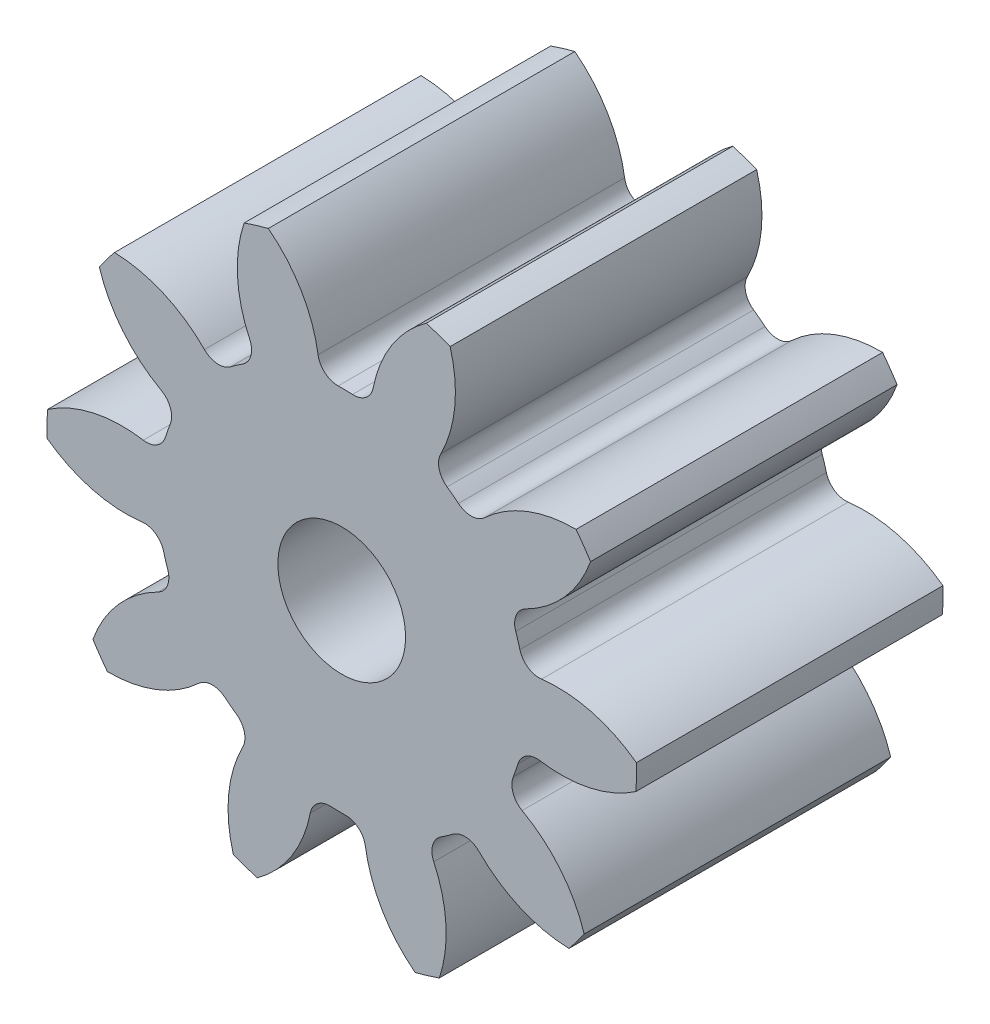
SolidWorks part; units mm, degrees
ref_plane "Front" through (0, 0, 0) normal (0, 0, 1) x (1, 0, 0)
ref_plane "Top" through (0, 0, 0) normal (0, 1, 0) x (1, 0, 0)
ref_plane "Right" through (0, 0, 0) normal (1, 0, 0) x (0, 0, -1)
sketch "Sketch3" plane through (0, 0, 0) normal (0, 0, 1) x (1, 0, 0)
  circle A0 centre (0, 0) radius 5.8615
  dimension "od" = 11.7231
extrude "gearBody" add sketch "Sketch3" along normal blind 6.096
sketch "Sketch2" plane through (0, 0, 0) normal (0, 0, 1) x (1, 0, 0)
  line L0 (0, 0) -> (4.3691, 1.8097) construction
  line L1 (4.8681, -4.7499) -> (0, 0) construction
  line L2 (0, 0) -> (36.3143, 0) construction
  line L3 (4.8215, -0.7828) -> (4.2715, -2.3694) construction
  line L5 (4.5465, -1.5761) -> (0, 0) construction
  line L7 (0, 0) -> (4.729, 0) construction
  arc A0 (4.6599, -0.8059) -> (4.1588, -2.2512) centre (0, 0) ccw construction
  arc A1 (5.8501, -0.3657) -> (4.8212, -3.3337) centre (0, 0) ccw construction
  arc A2 (4.8215, -0.7828) -> (4.2715, -2.3694) centre (0, 0) ccw construction
  arc A3 (3.4104, -1.3327) -> (3.5035, -1.0641) centre (0, 0) ccw
  arc A4 (4.8681, -4.7499) -> (3.5875, -1.8239) centre (2.3115, -4.1256) ccw
  arc A5 (4.8681, -4.7499) -> (6.7635, 0.7176) centre (0, 0) ccw
  arc A6 (6.7635, 0.7176) -> (3.9466, -0.7879) centre (4.3691, 1.8097) cw
  arc A7 (3.5035, -1.0641) -> (3.9466, -0.7879) centre (3.883, -1.1794) cw
  arc A8 (3.5875, -1.8239) -> (3.4104, -1.3327) centre (3.7798, -1.477) cw
  point P6 (6.7635, 0.7176)
  point P22 (4.8681, -4.7499)
  dimension "baseDia" = 9.4581
  dimension "od" = 11.7231
  dimension "pd" = 9.7692
  dimension "rd" = 7.323
  dimension "rFillet" = 0.3966
  dimension "pointX" = 6.7635
  dimension "pointY" = 0.7176
  dimension "CTT" = 1.5865
  dimension "flankCenterAngle" = 22.5
extrude "toothCut" cut sketch "Sketch2" along normal through all
pattern_circular "CirPattern1" count 10 over 360 about axis through (0, 0, 6.096) along (0, 0, -1) of "toothCut"
ref_axis "toothSpace" through (0, 0, 0) along (0.9448, -0.3275, 0)
ref_axis "Axis2" through (4.6739, -3.5373, 0) along (-0.7974, 0.6035, 0)
sketch "hub1Dia" plane through (0, 0, 0) normal (0, 0, -1) x (-1, 0, 0)
  circle A0 centre (0, 0) radius 12.7
  dimension "hub1Dia" = 25.4
sketch "hub2Dia" plane through (0, 0, 6.096) normal (0, 0, 1) x (1, 0, 0)
  circle A0 centre (0, 0) radius 12.7
  dimension "hub2dia" = 25.4
sketch "boreDia" plane through (0, 0, 0) normal (0, 0, 1) x (1, 0, 0)
  circle A0 centre (0, 0) radius 1.27
  dimension "boreDia" = 2.54
extrude "bore" cut sketch "boreDia" against normal mid plane 25400
sketch "kwy1sketch" plane through (0, 0, 0) normal (0, 0, 1) x (1, 0, 0)
  line L0 (-5.0268, 3.0347) -> (0, 0) construction
  line L1 (29.3956, -2.9115) -> (16.2682, -24.6561)
  line L2 (16.2682, -24.6561) -> (-10.9126, -8.2469)
  line L3 (29.3956, -2.9115) -> (2.2148, 13.4978)
  line L4 (-10.9126, -8.2469) -> (0, 0)
  line L5 (0, 0) -> (2.2148, 13.4978)
  line L6 (0, 0) -> (3.4595, -1.1993) construction
  line L7 (22.8319, -13.7838) -> (0, 0) construction
  arc A7 (3.4104, -1.3327) -> (3.5035, -1.0641) centre (0, 0) ccw construction
  point P9 (22.8319, -13.7838)
  point P13 (-0.8385, 0.5062)
  dimension "kwy1width" = 25.4
  dimension "kwy1depth" = 26.67
  dimension "kwy1angle" = 12
  dimension "kwy1Depth2" = 31.75
sketch "kwy2sketch" plane through (0, 0, 0) normal (0, 0, 1) x (1, 0, 0)
  line L0 (3.4595, -1.1993) -> (0, 0) construction
  line L1 (0, 0) -> (-3.9391, -0.9734) construction
  line L2 (22.8446, 18.7271) -> (28.9379, -5.9312)
  line L3 (28.9379, -5.9312) -> (-1.885, -13.5478)
  line L4 (22.8446, 18.7271) -> (-7.9783, 11.1105)
  line L5 (-1.885, -13.5478) -> (0, 0)
  line L6 (0, 0) -> (-7.9783, 11.1105)
  arc A2 (3.4104, -1.3327) -> (3.5035, -1.0641) centre (0, 0) ccw construction
  point P10 (25.8912, 6.398)
  dimension "kwy2angle" = 33
  dimension "kwy2Width" = 25.4
  dimension "kwy2depth" = 26.67
  dimension "kwy2Depth2" = 31.75
sketch "kwy3sketch" plane through (0, 0, 0) normal (0, 0, 1) x (1, 0, 0)
  line L0 (3.4595, -1.1993) -> (0, 0) construction
  line L1 (0, 0) -> (-1.5171, -2.513) construction
  line L2 (2.9115, 29.3956) -> (24.6561, 16.2682)
  line L3 (24.6561, 16.2682) -> (8.2469, -10.9126)
  line L4 (2.9115, 29.3956) -> (-13.4978, 2.2148)
  line L5 (8.2469, -10.9126) -> (0, 0)
  line L6 (-13.4978, 2.2148) -> (0, 0)
  point P10 (13.7838, 22.8319)
  dimension "kwy3angle" = 78
  dimension "kwy3depth" = 26.67
  dimension "kwy3width" = 25.4
  dimension "kwy3Depth2" = 31.75
sketch "kwy4sketch" plane through (0, 0, 0) normal (0, 0, 1) x (1, 0, 0)
  line L0 (3.4595, -1.1993) -> (0, 0) construction
  line L1 (0, 0) -> (0.5506, -2.2282) construction
  line L2 (5.9312, 28.9379) -> (-18.7271, 22.8446)
  line L3 (-18.7271, 22.8446) -> (-11.1105, -7.9783)
  line L4 (-11.1105, -7.9783) -> (0, 0)
  line L5 (13.5478, -1.885) -> (0, 0)
  line L6 (5.9312, 28.9379) -> (13.5478, -1.885)
  point P15 (-6.398, 25.8912)
  dimension "kwy4angle" = 123
  dimension "kwy4depth" = 26.67
  dimension "kwy4width" = 25.4
  dimension "kwy4Depth2" = 31.75
sketch "kwy5sketch" plane through (0, 0, 0) normal (0, 0, 1) x (1, 0, 0)
  line L0 (3.4595, -1.1993) -> (0, 0) construction
  line L1 (0, 0) -> (1.6876, -1.0188) construction
  line L2 (-16.2682, 24.6561) -> (-29.3956, 2.9115)
  line L3 (-29.3956, 2.9115) -> (-2.2148, -13.4978)
  line L4 (-16.2682, 24.6561) -> (10.9126, 8.2469)
  line L5 (-2.2148, -13.4978) -> (0, 0)
  line L6 (10.9126, 8.2469) -> (0, 0)
  point P10 (-22.8319, 13.7838)
  dimension "kwy5width" = 25.4
  dimension "kwy5depth" = 26.67
  dimension "kwy5angle" = 168
  dimension "kwy5Depth2" = 31.75
sketch "kwy6sketch" plane through (0, 0, 0) normal (0, 0, 1) x (1, 0, 0)
  line L0 (3.4595, -1.1993) -> (0, 0) construction
  line L1 (0, 0) -> (1.9122, 0.4725) construction
  line L2 (-28.9379, 5.9312) -> (-22.8446, -18.7271)
  line L3 (-22.8446, -18.7271) -> (7.9783, -11.1105)
  line L4 (-28.9379, 5.9312) -> (1.885, 13.5478)
  line L5 (7.9783, -11.1105) -> (0, 0)
  line L6 (1.885, 13.5478) -> (0, 0)
  point P10 (-25.8912, -6.398)
  dimension "kwy6angle" = 213
  dimension "kwy6width" = 25.4
  dimension "kwy6depth" = 26.67
  dimension "kwy6Depth2" = 31.75
sketch "kwy7sketch" plane through (0, 0, 0) normal (0, 0, 1) x (1, 0, 0)
  line L0 (3.4595, -1.1993) -> (0, 0) construction
  line L1 (0, 0) -> (1.1405, 1.8891) construction
  line L2 (-24.6561, -16.2682) -> (-2.9115, -29.3956)
  line L3 (-24.6561, -16.2682) -> (-8.2469, 10.9126)
  line L4 (-2.9115, -29.3956) -> (13.4978, -2.2148)
  line L5 (-8.2469, 10.9126) -> (0, 0)
  line L6 (13.4978, -2.2148) -> (0, 0)
  point P10 (-13.7838, -22.8319)
  dimension "kwy7angle" = 78
  dimension "kwy7width" = 25.4
  dimension "kwy7depth" = 26.67
  dimension "kwy7angle1" = 258
  dimension "kwy7Depth2" = 31.75
sketch "kwy8sketch" plane through (0, 0, 0) normal (0, 0, 1) x (1, 0, 0)
  line L0 (3.4595, -1.1993) -> (0, 0) construction
  line L1 (0, 0) -> (-0.4703, 1.9032) construction
  line L2 (-5.9312, -28.9379) -> (18.7271, -22.8446)
  line L3 (18.7271, -22.8446) -> (11.1105, 7.9783)
  line L4 (-5.9312, -28.9379) -> (-13.5478, 1.885)
  line L5 (11.1105, 7.9783) -> (0, 0)
  line L6 (-13.5478, 1.885) -> (0, 0)
  point P10 (6.398, -25.8912)
  dimension "kwy8angle" = 303
  dimension "kwy8width" = 25.4
  dimension "kwy8depth" = 26.67
  dimension "kwy8Depth2" = 31.75
sketch "centerLine" plane through (0, 0, 0) normal (0, 1, 0) x (1, 0, 0)
  line L0 (0, 36.4807) -> (0, -59.6309) construction
ref_plane "CB1plane" through (0, 0, 0) normal (0, 0, -1) x (-1, 0, 0)
sketch "CB1diameter" plane through (0, 0, 0) normal (0, 0, -1) x (-1, 0, 0)
  circle A0 centre (0, 0) radius 12.7
  dimension "CB1diameter" = 25.4
ref_plane "CB2plane" through (0, 0, 6.096) normal (0, 0, 1) x (1, 0, 0)
sketch "CB2diameter" plane through (0, 0, 6.096) normal (0, 0, 1) x (1, 0, 0)
  circle A0 centre (0, 0) radius 12.7
  dimension "CB2diameter" = 25.4
ref_axis "Axis1" through (0, 0, 50) along (0, 0, -1)
